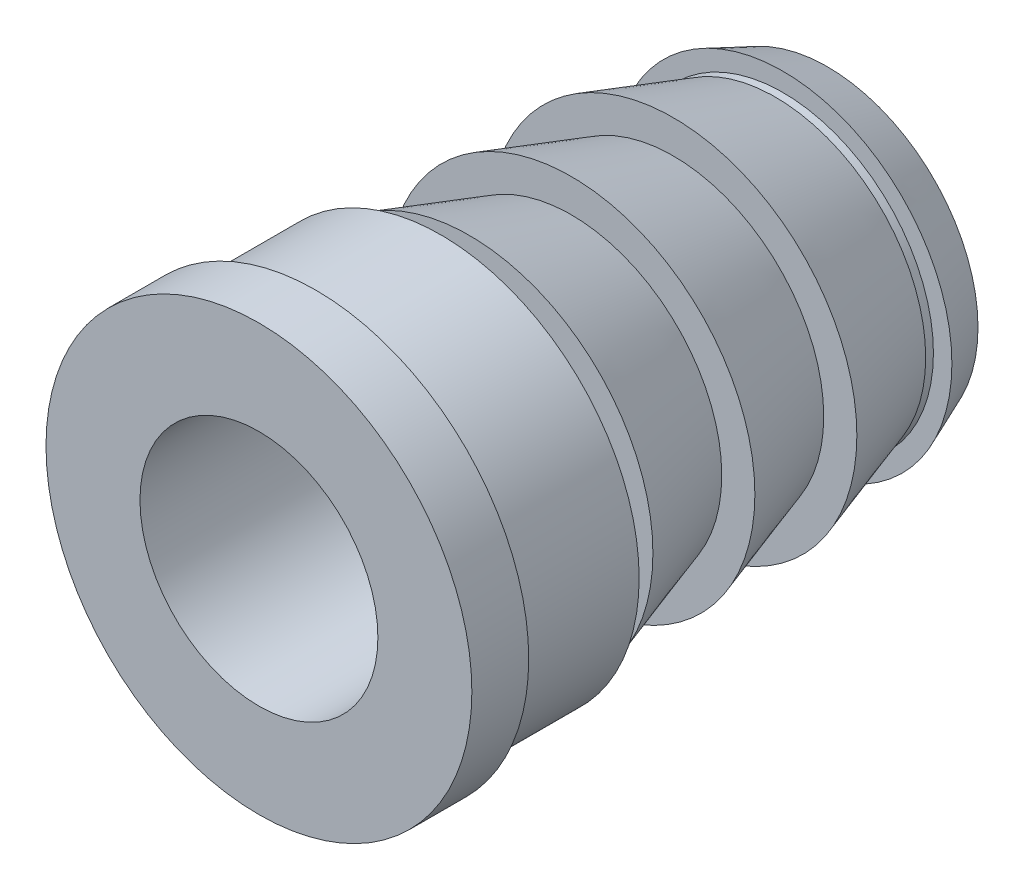
SolidWorks part; units mm, degrees
material "Brass"
ref_plane "Front Plane" through (0, 0, 0) normal (0, 0, 1) x (1, 0, 0)
ref_plane "Top Plane" through (0, 0, 0) normal (0, 1, 0) x (1, 0, 0)
ref_plane "Right Plane" through (0, 0, 0) normal (1, 0, 0) x (0, 0, -1)
sketch "Sketch1" plane through (0, 0, 0) normal (1, 0, 0) x (0, 0, -1)
  line L0 (-2.39, 0) -> (2.39, 0) construction
  line L1 (-2.39, 1) -> (-2.39, 1.79)
  line L2 (-2.39, 1.79) -> (-1.912, 1.79)
  line L3 (-1.912, 1.79) -> (-1.912, 1.6667)
  line L4 (-1.912, 1.6667) -> (-0.8604, 1.6667)
  line L5 (-0.8604, 1.6667) -> (-0.8604, 1.2648)
  line L9 (-0.6214, 1.5433) -> (0.2358, 1.2648)
  line L13 (0.2358, 1.2648) -> (2.0153, 1.2648)
  line L14 (2.0153, 1.2648) -> (2.0153, 1.42)
  line L15 (2.0153, 1.42) -> (2.39, 1.2648)
  line L16 (2.39, 1.2648) -> (2.39, 1)
  line L17 (-2.39, 1.42) -> (2.39, 1.42) construction
  line L18 (2.39, 0) -> (2.39, 1.42) construction
  line L19 (-2.39, 0) -> (-2.39, 1.79) construction
  line L21 (-2.39, 1) -> (2.39, 1)
  line L22 (-0.8604, 1.2648) -> (-0.6214, 1.2648)
  line L23 (-2.765, 1.0433) -> (-2.565, 0.6969) construction
  line L24 (-2.39, -1.42) -> (2.39, -1.42) construction
  line L25 (-2.565, 0.6969) -> (-2.365, 1.0433) construction
  line L26 (-2.365, 1.0433) -> (-2.765, 1.0433) construction
  line L27 (-2.74, 1) -> (-2.39, 1) construction
  line L28 (-2.565, 1.0433) -> (-2.565, 1) construction
  line L29 (-2.565, 1) -> (-2.565, 0.7402) construction
  line L30 (-2.565, 0.7402) -> (-2.565, 0.6969) construction
  line L31 (-2.59, 0.7402) -> (-2.54, 0.7402)
  line L32 (-2.7525, 1.0217) -> (-2.3775, 1.0217)
  line L33 (-2.54, 0.7402) -> (-2.3775, 1.0217)
  line L34 (-2.59, 0.7402) -> (-2.7525, 1.0217)
  line L35 (-2.39, 1.36) -> (2.39, 1.36) construction
  line L36 (-2.39, -1.36) -> (2.39, -1.36) construction
  line L37 (-0.6214, 1.2648) -> (-0.6214, 1.5433)
  line L40 (-1.3862, 1.6667) -> (-1.3862, 1.5433) construction
  line L41 (-1.3862, 1.5433) -> (-1.3862, 1.42) construction
  point P36 (-2.565, 1.0217)
  dimension "Installed Length" = 4.78
  dimension "Dia A" = 3.58
  dimension "Dia B" = 2.84
  dimension "Thread Dia" = 2
  dimension "D6" = 22.5
  dimension "D4" = 18
  dimension "Thread Pitch" = 0.4
  dimension "D2" = 0.05
  dimension "Max Hole Dia" = 2.72
  dimension "D1" = 2.5296
  dimension "D3" = 0.478
  dimension "Knurling Length" = 1.0516
  dimension "D5" = 0.239
ref_plane "Plane1" through (0, 0, 1.912) normal (0, 0, 1) x (1, 0, 0)
sketch "Sketch2" plane through (0, 0, 1.912) normal (0, 0, 1) x (1, 0, 0)
  line L0 (0, 0) -> (0, 1.6667) construction
  line L3 (-0.0582, 1.6657) -> (0, 0) construction
  line L4 (0.0582, 1.6657) -> (0, 0) construction
  line L5 (0, 0) -> (-0.3252, 1.6346) construction
  line L6 (0, 0) -> (0.3252, 1.6346) construction
  line L7 (0, 0) -> (1.1785, 1.1785) construction
  line L8 (0, 0) -> (0, -1.0433) construction
  line L9 (0, 0) -> (0.5217, -0.9035) construction
  line L13 (0.0582, 1.6657) -> (0.2653, 1.3339)
  line L14 (-0.0582, 1.6657) -> (-0.2653, 1.3339)
  line L15 (-0.2653, 1.3339) -> (0.2653, 1.3339)
  circle A0 centre (0, 0) radius 1.2648 construction
  circle A1 centre (0, 0) radius 1.6667 construction
  circle A3 centre (0, 0) radius 1.0433
  arc A6 (-0.0582, 1.6657) -> (0.0582, 1.6657) centre (0, 0) cw
  circle A7 centre (0, 0) radius 1.36 construction
  dimension "Knurl Angle" = 4
  dimension "Pattern Angle" = 22.5
  dimension "Helix Angle" = 45
  dimension "D1" = 30
sketch "Sketch3" plane through (0, 0, 0) normal (1, 0, 0) x (0, 0, -1)
  line L0 (-2.39, 1) -> (-2.39, 1.79) construction
  line L1 (-2.39, 1.79) -> (-1.912, 1.79) construction
  line L2 (-1.912, 1.79) -> (-1.912, 1.6667) construction
  line L3 (0.2358, 1.2648) -> (0.2358, 1.5433)
  line L4 (-0.8604, 1.6667) -> (-0.8604, 1.2648) construction
  line L5 (0.2358, 1.5433) -> (1.0931, 1.2648)
  line L6 (1.0931, 1.2648) -> (1.0931, 1.5433)
  line L7 (1.0931, 1.5433) -> (1.9503, 1.2648)
  line L8 (-0.6214, 1.5433) -> (0.2358, 1.2648) construction
  line L9 (1.9503, 1.2648) -> (2.0153, 1.2648)
  line L11 (-1.912, 1.6667) -> (-0.8604, 1.6667) construction
  line L12 (0.2358, 1.2648) -> (2.0153, 1.2648) construction
  line L13 (2.0153, 1.2648) -> (2.0153, 1.42) construction
  line L14 (2.0153, 1.42) -> (2.39, 1.2648) construction
  line L15 (2.39, 1.2648) -> (2.39, 1) construction
  line L16 (-2.39, 1) -> (2.39, 1) construction
  line L17 (-2.39, 1) -> (-2.39, 1.79)
  line L18 (-2.39, 1.79) -> (-1.912, 1.79)
  line L19 (-1.912, 1.79) -> (-1.912, 1.6667)
  line L21 (-0.8604, 1.6667) -> (-0.8604, 1.2648)
  line L25 (-0.6214, 1.5433) -> (0.2358, 1.2648)
  line L29 (0.2358, 1.2648) -> (2.0153, 1.2648) construction
  line L30 (2.0153, 1.2648) -> (2.0153, 1.42)
  line L31 (2.0153, 1.42) -> (2.39, 1.2648)
  line L32 (2.39, 1.2648) -> (2.39, 1)
  line L33 (-2.39, 1) -> (2.39, 1)
  line L36 (-0.6214, 1.2648) -> (-0.6214, 1.5433) construction
  line L37 (-0.8604, 1.2648) -> (-0.6214, 1.2648) construction
  line L40 (-1.912, 1.6667) -> (-0.8604, 1.6667)
  line L41 (-0.6214, 1.2648) -> (-0.6214, 1.5433)
  line L42 (-0.8604, 1.2648) -> (-0.6214, 1.2648)
revolve "Revolve1" add sketch "Sketch3" angle 360 about L0
sketch "Sketch4" [suppressed] plane through (0, 0, 1.912) normal (0, 0, 1) x (1, 0, 0)
  circle A2 centre (0, 0) radius 1.6667 construction
  circle A3 centre (0, 0) radius 1.6667
sketch "Sketch6" [suppressed] plane through (0, 0, 2.39) normal (0, 0, 1) x (1, 0, 0)
  circle A0 centre (0, 0) radius 1
curve "Helix/Spiral2" [suppressed] pitch 0.4 height 5.18 turns 12.95
sketch "Sketch7" [suppressed] plane through (0, 0, 0) normal (1, 0, 0) x (0, 0, -1)
  line L0 (-2.59, 0.7402) -> (-2.54, 0.7402) construction
  line L1 (-2.59, 0.7402) -> (-2.7525, 1.0217) construction
  line L2 (-2.7525, 1.0217) -> (-2.3775, 1.0217) construction
  line L3 (-2.54, 0.7402) -> (-2.3775, 1.0217) construction
  line L4 (-2.59, 0.7402) -> (-2.54, 0.7402)
  line L5 (-2.59, 0.7402) -> (-2.7525, 1.0217)
  line L6 (-2.7525, 1.0217) -> (-2.3775, 1.0217)
  line L7 (-2.54, 0.7402) -> (-2.3775, 1.0217)
sweep "Sweep1" [suppressed] add profiles "Sketch7" path "Helix/Spiral2"
sketch "Sketch8" [suppressed] plane through (0, 0, 2.39) normal (0, 0, 1) x (1, 0, 0)
  circle A0 centre (0, 0) radius 1.0433
extrude "Cut-Extrude1" [suppressed] cut sketch "Sketch8" against normal through all draft 45 and the other way through all
mirror "Mirror1" [suppressed] about plane through (0, 0, 0) normal (0, 0, 1)
curve "Helix/Spiral1" [suppressed] pitch 8.4128 height 1.0516 turns 0.125
sketch "Sketch9" [suppressed] plane through (0, 0, 1.912) normal (0, 0, 1) x (1, 0, 0)
  circle A3 centre (0, 0) radius 1.36 construction
  circle A4 centre (0, 0) radius 1.36
extrude "Cut-Extrude2" [suppressed] cut sketch "Sketch9" against normal up to vertex flip side to cut
sketch "Sketch5" [suppressed] plane through (0, 0, 1.912) normal (0, 0, 1) x (1, 0, 0)
  line L8 (-0.0582, 1.6657) -> (-0.2653, 1.3339) construction
  line L9 (0.0582, 1.6657) -> (0.2653, 1.3339) construction
  line L10 (-0.2653, 1.3339) -> (0.2653, 1.3339) construction
  line L11 (-0.0582, 1.6657) -> (-0.2653, 1.3339)
  line L12 (0.0582, 1.6657) -> (0.2653, 1.3339)
  line L13 (-0.2653, 1.3339) -> (0.2653, 1.3339)
  arc A7 (0.0582, 1.6657) -> (-0.0582, 1.6657) centre (0, 0) ccw construction
  arc A8 (0.0582, 1.6657) -> (-0.0582, 1.6657) centre (0, 0) ccw
sweep "Sweep2" [suppressed] add profiles "Sketch5" path "Helix/Spiral1"
pattern_circular "CirPattern1" [suppressed] count 12 over 360 about axis through (0, 0, 2.39) along (0, 0, -1) of bodies 112
mirror "Mirror2" [suppressed] about plane through (0, 0, 0) normal (1, 0, 0)
sketch "Sketch11" [suppressed] plane through (0, 0, 0) normal (1, 0, 0) x (0, 0, -1)
  line L0 (-0.6214, 1.2648) -> (-0.6214, 1.5433) construction
  line L1 (-1.912, 1.79) -> (-1.912, 1.6667) construction
  line L2 (-0.8604, 1.2648) -> (-0.6214, 1.2648) construction
  line L3 (-0.8604, 1.6667) -> (-0.8604, 1.2648) construction
  line L4 (-1.912, 1.6667) -> (-0.8604, 1.6667) construction
  line L5 (-0.6214, 1.2648) -> (-0.6214, 1.79)
  line L6 (-1.912, 1.79) -> (-1.912, 1.6617)
  line L7 (-0.8654, 1.2648) -> (-0.6214, 1.2648)
  line L8 (-0.8604, 1.6667) -> (-0.8604, 1.2648) construction
  line L9 (-1.912, 1.6667) -> (-0.8604, 1.6667) construction
  line L10 (-2.39, 1.79) -> (-1.912, 1.79) construction
  line L11 (-0.6214, 1.79) -> (-1.912, 1.79)
  line L12 (-1.912, 1.6617) -> (-0.8654, 1.6617)
  line L13 (-0.8654, 1.6617) -> (-0.8654, 1.2648)
  dimension "D1" = 0.005
revolve "Cut-Revolve1" [suppressed] cut sketch "Sketch11" angle 360 about L0
equation "\"D4@Helix/Spiral1\"=\"Knurling Length@Sketch1\"*(360/\"Helix Angle@Sketch2\")"
equation "\"D3@Helix/Spiral1\"=\"Knurling Length@Sketch1\""
equation "\"D2@Sketch1\" = \"Thread Pitch@Sketch1\" / 8"
equation "\"D4@Helix/Spiral2\"=\"Thread Pitch@Sketch1\""
equation "\"D3@Helix/Spiral2\" = \"Installed Length@Sketch1\" + \"Thread Pitch@Sketch1\""
equation "\"D1@Sketch1\"=\"Max Hole Dia@Sketch1\"*.93"
equation "\"D3@Sketch1\"=\"Installed Length@Sketch1\"*.1"
equation "\"Knurling Length@Sketch1\"=\"Installed Length@Sketch1\" * .22"
equation "\"D1@CirPattern1\"=\"D3@CirPattern1\" / \"Pattern Angle@Sketch2\"-4"
equation "\"D5@Sketch1\"=\"Installed Length@Sketch1\"*.05"
